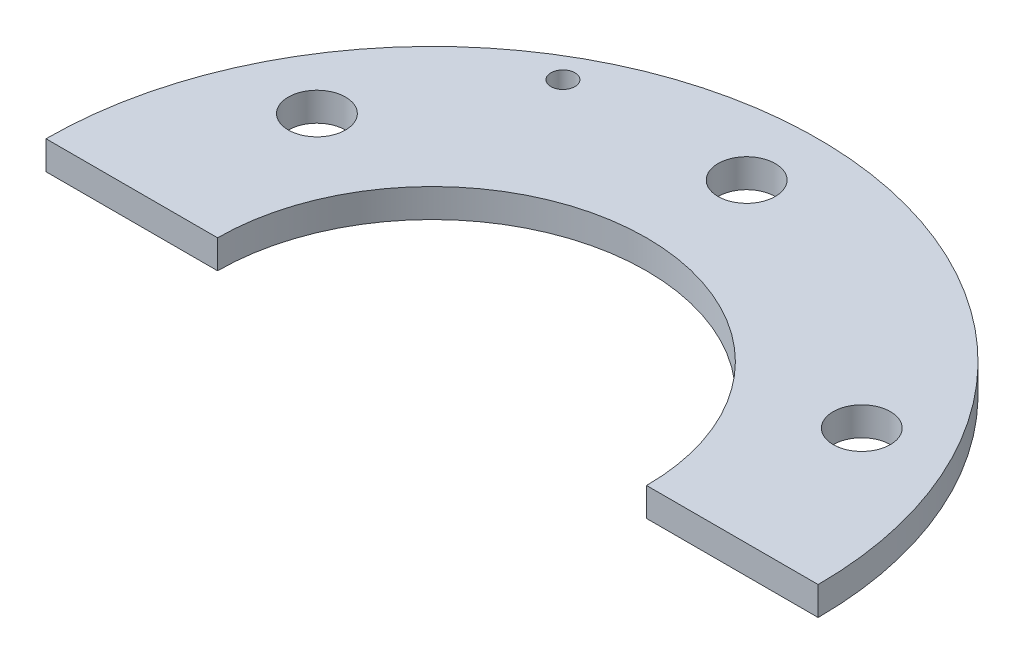
SolidWorks part; units mm, degrees
material "ABS"
ref_plane "Front Plane" through (0, 0, 0) normal (0, 0, 1) x (1, 0, 0)
ref_plane "Top Plane" through (0, 0, 0) normal (0, 1, 0) x (1, 0, 0)
ref_plane "Right Plane" through (0, 0, 0) normal (1, 0, 0) x (0, 0, -1)
sketch "Sketch1" plane through (0, 0, 0) normal (0, 1, 0) x (1, 0, 0)
  circle A0 centre (0, 0) radius 13.5
  dimension "D1" = 27
extrude "Boss-Extrude1" add sketch "Sketch1" along normal blind 1
sketch "Sketch19" plane through (0, 1, 0) normal (0, 1, 0) x (1, 0, 0)
  circle A0 centre (0, 11) radius 1
  circle A1 centre (9.5263, 5.5) radius 1
  circle A2 centre (9.5263, -5.5) radius 1
  circle A3 centre (0, -11) radius 1
  circle A4 centre (-9.5263, -5.5) radius 1
  circle A5 centre (-9.5263, 5.5) radius 1
  point P13 (0, 0)
  dimension "D1" = 2
  dimension "D2" = 11
  dimension "D3" = 6
extrude "Cut-Extrude1" cut sketch "Sketch19" against normal through all both and the other way through all
sketch "Sketch20" plane through (0, 1, 0) normal (0, 1, 0) x (1, 0, 0)
  circle A0 centre (0, 0) radius 7.5
  dimension "D1" = 15
extrude "Cut-Extrude2" cut sketch "Sketch20" against normal through all both and the other way through all
sketch "Sketch21" plane through (0, 0, 0) normal (0, 0, 1) x (1, 0, 0)
  line L1 (-36.7533, 32.3113) -> (29.1209, 32.3113)
  line L2 (-36.7533, 32.3113) -> (-36.7533, -19.668)
  line L3 (-36.7533, -19.668) -> (29.1209, -19.668)
  line L4 (29.1209, 32.3113) -> (29.1209, -19.668)
extrude "Cut-Extrude3" cut sketch "Sketch21" along normal through all
sketch "Sketch22" plane through (0, 1, 0) normal (0, 1, 0) x (1, 0, 0)
  line L0 (-9.5263, 5.5) -> (0, 11)
  line L1 (-6.25, 10.8253) -> (0, 0) construction
  circle A0 centre (-6.25, 10.8253) radius 0.42
  point P7 (-4.7631, 8.25)
  dimension "D1" = 0.84
  dimension "D2" = 12.5
  dimension "D3" = 0
extrude "Cut-Extrude4" cut sketch "Sketch22" against normal through all both and the other way through all contours L0 A0 | L0 L1 A0 | L1 L0 A0 region at (-6.25, 1, -10.8253)
